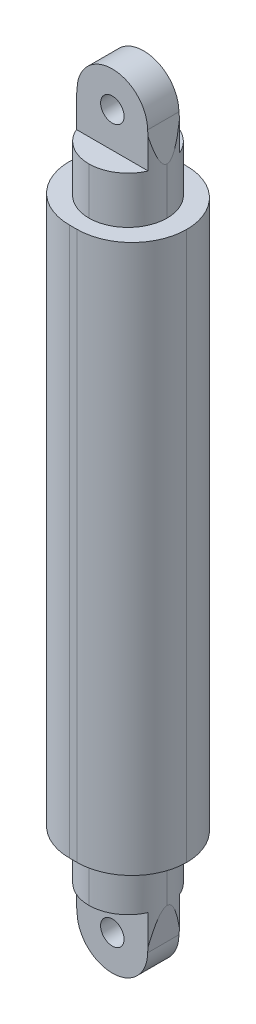
SolidWorks part; units mm, degrees
ref_plane "Front Plane" through (0, 0, 0) normal (0, 0, 1) x (1, 0, 0)
ref_plane "Top Plane" through (0, 0, 0) normal (0, 1, 0) x (1, 0, 0)
ref_plane "Right Plane" through (0, 0, 0) normal (1, 0, 0) x (0, 0, -1)
sketch "Sketch2" plane through (0, 0, 0) normal (0, 0, 1) x (1, 0, 0)
  line L1 (-5, -50) -> (5, -50)
  line L2 (-5, -50) -> (-5, 50)
  line L3 (-5, 50) -> (5, 50)
  line L4 (5, -50) -> (5, 50)
  line L5 (-5, -50) -> (5, 50) construction
  line L6 (-5, 50) -> (5, -50) construction
  point P0 (0, 0)
  dimension "D1" = 100
  dimension "D2" = 10
extrude "Boss-Extrude1" add sketch "Sketch2" along normal blind 10
fillet "Fillet1" radius 5 4 edges at (-5, 0, 0) (5, 0, 0) (5, 0, 10) (-5, 0, 10)
sketch "Sketch3" plane through (0, 0, 0) normal (0, 0, 1) x (1, 0, 0)
  line L0 (-5, -50) -> (-5, 50) construction
  line L1 (5, -50) -> (-5, -50)
  line L2 (5, -50) -> (5, -41)
  line L3 (5, -41) -> (-5, -41)
  line L4 (-5, -50) -> (-5, -41)
  line L5 (0, -50) -> (0, 50) construction
  line L6 (-5, -41) -> (-4.5, -45.5)
  line L7 (5, -41) -> (4.5, -45.5)
  arc A0 (-4.5, -45.5) -> (4.5, -45.5) centre (0, -45.5) ccw
  dimension "D1" = 4.5
  dimension "D2" = 9
  dimension "D3" = 9
extrude "Cut-Extrude1" cut sketch "Sketch3" along normal blind 3 contours L6 A0 L7 L3 | A0 L1 L2 L7 | A0 L6 L4 L1 region at (4.0557, -47.9043, 0) region at (-4.0557, -47.9043, 0) region at (0, -45.0021, 0)
extrude "Cut-Extrude2" cut sketch "Sketch3<2>" along normal blind 3 from offset 7 contours L2 L3 L4 L1
sketch "Sketch3<2>" plane through (0, 0, 0) normal (0, 0, 1) x (1, 0, 0) same geometry as "Sketch3"
mirror "Mirror1" about plane through (0, 0, 0) normal (0, 1, 0) of "Cut-Extrude2", "Cut-Extrude1"
extrude "Cut-Extrude4" cut sketch "Sketch3<4>" against normal blind 4 and the other way through all contours A0 L1 L2 L7 | A0 L6 L4 L1 region at (4.0557, -47.9043, 0) region at (-4.0557, -47.9043, 0)
sketch "Sketch3<4>" plane through (0, 0, 0) normal (0, 0, 1) x (1, 0, 0) same geometry as "Sketch3"
sketch "Sketch7" plane through (0, 0, 3) normal (0, 0, -1) x (-1, 0, 0)
  circle A0 centre (0, -45.5) radius 1.5
  dimension "D1" = 3
extrude "Cut-Extrude5" cut sketch "Sketch7" against normal through all
mirror "Mirror3" about plane through (0, 0, 0) normal (0, 1, 0) of "Cut-Extrude5"
mirror "Mirror4" about plane through (0, 0, 0) normal (0, 1, 0) of "Cut-Extrude4"
ref_plane "Plane1" through (0, 0, 5) normal (0, 0, 1) x (1, 0, 0)
sketch "Sketch9" plane through (0, 0, 5) normal (0, 0, 1) x (1, 0, 0)
  line L0 (-7.5, -35) -> (7.5, -35)
  line L1 (-7.5, -35) -> (-7.5, 35)
  line L2 (-7.5, 35) -> (7.5, 35)
  line L3 (7.5, -35) -> (7.5, 35)
  line L4 (-7.5, -35) -> (7.5, 35) construction
  line L5 (-7.5, 35) -> (7.5, -35) construction
  line L6 (0, 35) -> (0, -35) construction
  point P0 (0, 0)
  dimension "D1" = 70
  dimension "D2" = 15
extrude "Boss-Extrude2" add sketch "Sketch9" along normal blind 7 and the other way blind 7
fillet "Fillet3" radius 7 4 edges at (-7.5, 0, 12) (7.5, 0, 12) (7.5, 0, -2) (-7.5, 0, -2)
